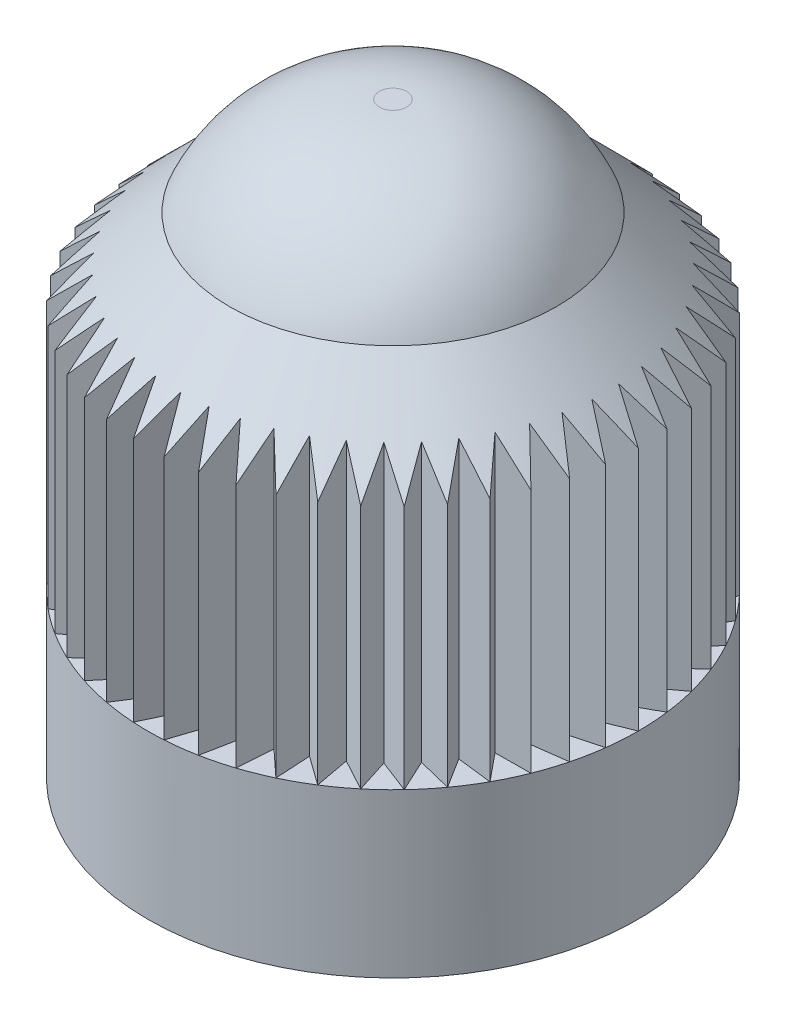
SolidWorks part; units mm, degrees
ref_plane "Спереди" through (0, 0, 0) normal (0, 0, 1) x (1, 0, 0)
ref_plane "Сверху" through (0, 0, 0) normal (0, 1, 0) x (1, 0, 0)
ref_plane "Справа" through (0, 0, 0) normal (1, 0, 0) x (0, 0, -1)
sketch "Sketch1" plane through (0, 0, 0) normal (0, 1, 0) x (1, 0, 0)
  circle A0 centre (0, 0) radius 7.5
  dimension "D1" = 15
extrude "Boss-Extrude1" add sketch "Sketch1" along normal blind 18
sketch "Sketch2" plane through (0, 0, 0) normal (0, -1, 0) x (1, 0, 0)
  circle A0 centre (0, 0) radius 6.5
  dimension "D1" = 13
extrude "Cut-Extrude1" cut sketch "Sketch2" against normal blind 0.01
sketch "Sketch3" plane through (0, 0.01, 0) normal (0, -1, 0) x (1, 0, 0)
  line L0 (-1.7426, -2.6839) -> (3.1363, -0.6354)
  line L1 (0.6968, -1.6596) -> (-1.2388, 2.9505) construction
  circle A0 centre (0, 0) radius 3.2 construction
  arc A1 (-1.7426, -2.6839) -> (3.1363, -0.6354) centre (0, 0) cw
  dimension "D1" = 6.4
  dimension "D2" = 5
extrude "Cut-Extrude2" cut sketch "Sketch3" against normal blind 14
chamfer "Chamfer1" distance 1 angle 30 1 edges at (0, 0, -6.5)
sketch "Sketch4" plane through (0, 18, 0) normal (0, 1, 0) x (1, 0, 0)
  circle A0 centre (0, 0) radius 5
  dimension "D1" = 10
extrude "Cut-Extrude3" cut sketch "Sketch4" against normal blind 13 flip side to cut
chamfer "Chamfer2" distance 10 angle 45 1 edges at (0, 5, 5)
sketch "Sketch5" plane through (0, 18, 0) normal (0, 1, 0) x (1, 0, 0)
  line L0 (2.3986, -6.0413) -> (2.3244, -7.1307)
  line L1 (2.3244, -7.1307) -> (1.6225, -6.2942)
  line L2 (1.6225, -6.2942) -> (1.4124, -7.3658)
  line L3 (1.4124, -7.3658) -> (0.8208, -6.448)
  line L4 (0.8208, -6.448) -> (0.4781, -7.4847)
  line L5 (0.4781, -7.4847) -> (0.0062, -6.5)
  line L6 (0.0062, -6.5) -> (-0.4638, -7.4856)
  line L7 (-0.4638, -7.4856) -> (-0.8085, -6.4495)
  line L8 (-0.8085, -6.4495) -> (-1.3983, -7.3685)
  line L9 (-1.3983, -7.3685) -> (-1.6105, -6.2973)
  line L10 (-1.6105, -6.2973) -> (-2.3108, -7.1351)
  line L11 (-2.3108, -7.1351) -> (-2.3871, -6.0458)
  line L12 (-2.3871, -6.0458) -> (-3.1869, -6.7892)
  line L13 (-3.1869, -6.7892) -> (-3.126, -5.699)
  line L14 (-3.126, -5.699) -> (-4.0127, -6.3363)
  line L15 (-4.0127, -6.3363) -> (-3.8156, -5.2622)
  line L16 (-3.8156, -5.2622) -> (-4.7752, -5.7834)
  line L17 (-4.7752, -5.7834) -> (-4.445, -4.7425)
  line L18 (-4.445, -4.7425) -> (-5.4624, -5.1393)
  line L19 (-5.4624, -5.1393) -> (-5.0044, -4.148)
  line L20 (-5.0044, -4.148) -> (-6.0634, -4.4142)
  line L21 (-6.0634, -4.4142) -> (-5.4848, -3.4881)
  line L22 (-5.4848, -3.4881) -> (-6.5689, -3.6194)
  line L23 (-6.5689, -3.6194) -> (-5.8787, -2.7732)
  line L24 (-5.8787, -2.7732) -> (-6.9707, -2.7676)
  line L25 (-6.9707, -2.7676) -> (-6.18, -2.0145)
  line L26 (-6.18, -2.0145) -> (-7.2626, -1.8721)
  line L27 (-7.2626, -1.8721) -> (-6.3837, -1.2241)
  line L28 (-6.3837, -1.2241) -> (-7.44, -0.9471)
  line L29 (-7.44, -0.9471) -> (-6.4868, -0.4143)
  line L30 (-6.4868, -0.4143) -> (-7.5, -0.0071)
  line L31 (-7.5, -0.0071) -> (-6.4876, 0.402)
  line L32 (-6.4876, 0.402) -> (-7.4418, 0.9329)
  line L33 (-7.4418, 0.9329) -> (-6.386, 1.2119)
  line L34 (-6.386, 1.2119) -> (-7.2661, 1.8583)
  line L35 (-7.2661, 1.8583) -> (-6.1838, 2.0027)
  line L36 (-6.1838, 2.0027) -> (-6.9759, 2.7543)
  line L37 (-6.9759, 2.7543) -> (-5.884, 2.762)
  line L38 (-5.884, 2.762) -> (-6.5757, 3.6069)
  line L39 (-6.5757, 3.6069) -> (-5.4914, 3.4777)
  line L40 (-5.4914, 3.4777) -> (-6.0718, 4.4026)
  line L41 (-6.0718, 4.4026) -> (-5.0123, 4.1385)
  line L42 (-5.0123, 4.1385) -> (-5.4721, 5.1289)
  line L43 (-5.4721, 5.1289) -> (-4.4541, 4.7341)
  line L44 (-4.4541, 4.7341) -> (-4.7862, 5.7743)
  line L45 (-4.7862, 5.7743) -> (-3.8256, 5.255)
  line L46 (-3.8256, 5.255) -> (-4.0247, 6.3286)
  line L47 (-4.0247, 6.3286) -> (-3.1368, 5.693)
  line L48 (-3.1368, 5.693) -> (-3.1998, 6.7832)
  line L49 (-3.1998, 6.7832) -> (-2.3986, 6.0413)
  line L50 (-2.3986, 6.0413) -> (-2.3244, 7.1307)
  line L51 (-2.3244, 7.1307) -> (-1.6225, 6.2942)
  line L52 (-1.6225, 6.2942) -> (-1.4124, 7.3658)
  line L53 (-1.4124, 7.3658) -> (-0.8208, 6.448)
  line L54 (-0.8208, 6.448) -> (-0.4781, 7.4847)
  line L55 (-0.4781, 7.4847) -> (-0.0062, 6.5)
  line L56 (-0.0062, 6.5) -> (0.4638, 7.4856)
  line L57 (0.4638, 7.4856) -> (0.8085, 6.4495)
  line L58 (0.8085, 6.4495) -> (1.3983, 7.3685)
  line L59 (1.3983, 7.3685) -> (1.6105, 6.2973)
  line L60 (1.6105, 6.2973) -> (2.3108, 7.1351)
  line L61 (2.3108, 7.1351) -> (2.3871, 6.0458)
  line L62 (2.3871, 6.0458) -> (3.1869, 6.7892)
  line L63 (3.1869, 6.7892) -> (3.126, 5.699)
  line L64 (3.126, 5.699) -> (4.0127, 6.3363)
  line L65 (4.0127, 6.3363) -> (3.8156, 5.2622)
  line L66 (3.8156, 5.2622) -> (4.7752, 5.7834)
  line L67 (4.7752, 5.7834) -> (4.445, 4.7425)
  line L68 (4.445, 4.7425) -> (5.4624, 5.1393)
  line L69 (5.4624, 5.1393) -> (5.0044, 4.148)
  line L70 (5.0044, 4.148) -> (6.0634, 4.4142)
  line L71 (6.0634, 4.4142) -> (5.4848, 3.4881)
  line L72 (5.4848, 3.4881) -> (6.5689, 3.6194)
  line L73 (6.5689, 3.6194) -> (5.8787, 2.7732)
  line L74 (5.8787, 2.7732) -> (6.9707, 2.7676)
  line L75 (6.9707, 2.7676) -> (6.18, 2.0145)
  line L76 (6.18, 2.0145) -> (7.2626, 1.8721)
  line L77 (7.2626, 1.8721) -> (6.3837, 1.2241)
  line L78 (6.3837, 1.2241) -> (7.44, 0.9471)
  line L79 (7.44, 0.9471) -> (6.4868, 0.4143)
  line L80 (6.4868, 0.4143) -> (7.5, 0.0071)
  line L81 (7.5, 0.0071) -> (6.4876, -0.402)
  line L82 (6.4876, -0.402) -> (7.4418, -0.9329)
  line L83 (7.4418, -0.9329) -> (6.386, -1.2119)
  line L84 (6.386, -1.2119) -> (7.2661, -1.8583)
  line L85 (7.2661, -1.8583) -> (6.1838, -2.0027)
  line L86 (6.1838, -2.0027) -> (6.9759, -2.7543)
  line L87 (6.9759, -2.7543) -> (5.884, -2.762)
  line L88 (5.884, -2.762) -> (6.5757, -3.6069)
  line L89 (6.5757, -3.6069) -> (5.4914, -3.4777)
  line L90 (5.4914, -3.4777) -> (6.0718, -4.4026)
  line L91 (6.0718, -4.4026) -> (5.0123, -4.1385)
  line L92 (5.0123, -4.1385) -> (5.4721, -5.1289)
  line L93 (5.4721, -5.1289) -> (4.4541, -4.7341)
  line L94 (4.4541, -4.7341) -> (4.7862, -5.7743)
  line L95 (4.7862, -5.7743) -> (3.8256, -5.255)
  line L96 (3.8256, -5.255) -> (4.0247, -6.3286)
  line L97 (4.0247, -6.3286) -> (3.1368, -5.693)
  line L98 (3.1368, -5.693) -> (3.1998, -6.7832)
  line L99 (3.1998, -6.7832) -> (2.3986, -6.0413)
  circle A0 centre (0, 0) radius 6.5 construction
  circle A2 centre (0, 0) radius 7.5 construction
  point P156 (0, 0)
  dimension "D1" = 13
  dimension "D2" = 50
extrude "Cut-Extrude4" cut sketch "Sketch5" against normal blind 13 flip side to cut
fillet "Fillet1" radius 5 1 edges at (0, 18, 5)
sketch "Sketch6" plane through (0, 0.01, 0) normal (0, -1, 0) x (1, 0, 0)
  circle A0 centre (0, 0) radius 12.6173
extrude "Cut-Extrude5" cut sketch "Sketch6" along normal blind 10
chamfer "Chamfer3" distance 0.5 angle 70 2 edges at (-1.2388, 0.01, 2.9505) (0.6968, 0.01, -1.6596)
